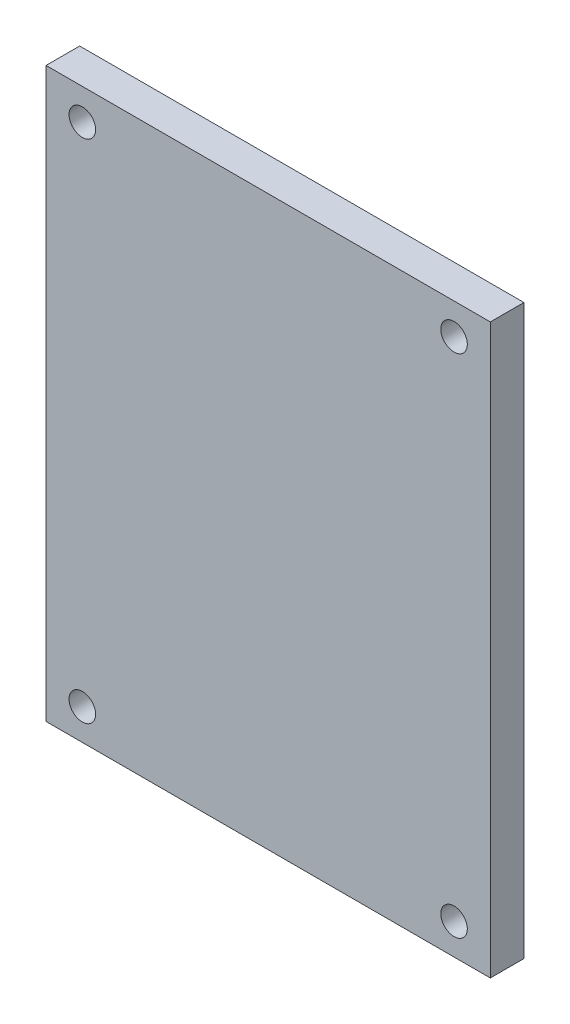
SolidWorks part; units mm, degrees
ref_plane "Front Plane" through (0, 0, 0) normal (0, 0, 1) x (1, 0, 0)
ref_plane "Top Plane" through (0, 0, 0) normal (0, 1, 0) x (1, 0, 0)
ref_plane "Right Plane" through (0, 0, 0) normal (1, 0, 0) x (0, 0, -1)
sketch "Sketch1" plane through (0, 0, 0) normal (0, 0, 1) x (1, 0, 0)
  line L0 (0, 40.767) -> (63.754, 40.767) construction
  line L1 (0, 0) -> (63.754, 0)
  line L2 (0, 0) -> (0, 81.534)
  line L3 (0, 81.534) -> (63.754, 81.534)
  line L4 (63.754, 0) -> (63.754, 81.534)
  line L5 (31.877, 81.534) -> (31.877, 0) construction
  circle A0 centre (5.207, 77.089) radius 1.905
  circle A1 centre (58.547, 77.089) radius 1.905
  circle A2 centre (5.207, 4.445) radius 1.905
  circle A3 centre (58.547, 4.445) radius 1.905
  dimension "D3" = 3.81
  dimension "D4" = 3.81
  dimension "D5" = 3.81
  dimension "D6" = 3.81
  dimension "D1" = 81.534
  dimension "D2" = 63.754
  dimension "D7" = 72.644
  dimension "D8" = 53.34
  dimension "D9" = 53.34
  dimension "D10" = 72.644
  dimension "D11" = 36.322
  dimension "D12" = 26.67
extrude "Boss-Extrude1" add sketch "Sketch1" along normal blind 4.826
equation "\"MDF\"= 0.19in"
equation "\"PVCID\" = 2.067in"
equation "\"PVCOD\" = 2.375in"
equation "\"GenDiameter\"= 60mm"
equation "\"GenCutDiameter\" = 1.8in"
equation "\"GenCutDistance\" = 1"
equation "\"TowerHeight\" = 6in"
equation "\"TowerFrontBase\" = 3in"
equation "\"FunnelHeight\" = 1in"
equation "\"FunnelAngle\" = 20"
equation "\"TowerSideBase\" = 3in"
equation "\"TowerPanelLength\" = 2in"
equation "\"TowerPanelLeeway\" = 0.5in"
equation "\"BaseLength\" = 9in"
equation "\"BaseWidth\" = 10in"
equation "\"WheelHoleLength\" = 3.25in"
equation "\"WheelHoleWidth\" = 26mm"
equation "\"WheelHoleFromBack\" = 1in"
equation "\"DropLength\" = 1in"
equation "\"DropWidth\" = 8.5in"
equation "\"BumperWidth\" = 1in"
equation "\"SmallHexDiameter\" = 0.185in"
equation "\"SmallHexHeight\" = 0.701in"
equation "\"ScrewSize\" = 0.106in"
equation "\"BigHexDiameter\" = 0.251in"
equation "\"BigHexHeight\" = 0.374in"
equation "\"PCBThickness\" = 0.066in"
equation "\"ConnectorHeight\" = 0.517in"
equation "\"BoardHeight\" = 0.583in"
equation "\"UnoStackHeight\" = 1.351in"
equation "\"UnoStackWidth\" = 3.053in"
equation "\"UnoStackLength\" = 3.152in"
equation "\"HBridgeWidth\" = 1.797in"
equation "\"HBridgeLength\" = 2.236in"
equation "\"DSWidth\" = 1.820in"
equation "\"DSLength\" = 1.833in"
equation "\"StepperWidth\" = 1.799in"
equation "\"StepperLength\" = 2.248in"
equation "\"ULNWidth\" = 1.304in"
equation "\"ULNLength\" = 1.545in"
equation "\"VSwitchHeight\" = 0.392in"
equation "\"VSwitchWidth\" = 0.637in"
equation "\"VSwitchLength\" = 1.097in"
equation "\"SkateWheelDiameter\" = 80mm"
equation "\"SkateWheelThickness\" = 24mm"
equation "\"BaseDistance\" = 3in"
equation "\"DummyVar\" = 2in"
equation "\"D1@Boss-Extrude1\"=\"MDF\""
